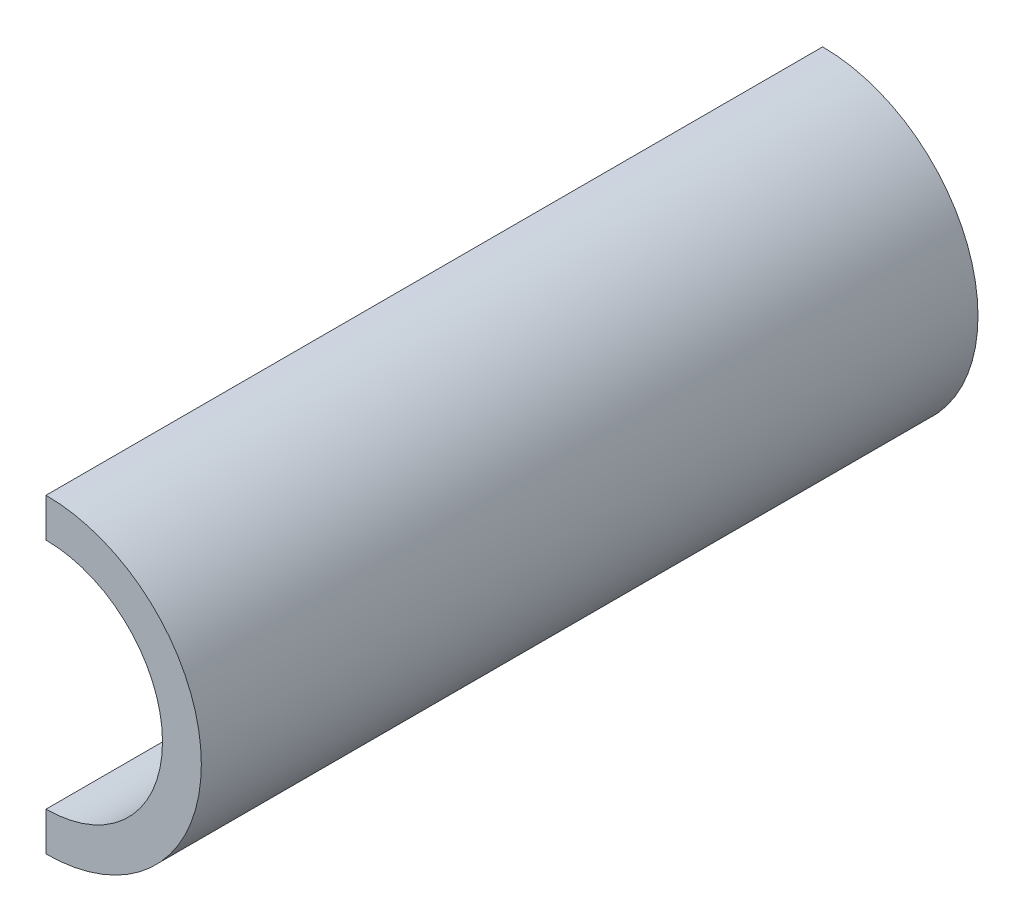
SolidWorks part; units mm, degrees
material "1.0037 (S235JR)"
ref_plane "E_Rechts" through (0, 0, 0) normal (0, 0, 1) x (1, 0, 0)
ref_plane "E_Oben" through (0, 0, 0) normal (0, 1, 0) x (1, 0, 0)
ref_plane "E_Vorne" through (0, 0, 0) normal (1, 0, 0) x (0, 0, -1)
sketch "Skizze1" plane through (0, 0, 0) normal (0, 0, 1) x (1, 0, 0)
  line L0 (0, 40) -> (0, 30)
  line L1 (0, -30) -> (0, -40)
  arc A0 (0, -40) -> (0, 40) centre (0, 0) ccw
  arc A1 (0, -30) -> (0, 30) centre (0, 0) ccw
extrude "Aufsatz-Linear austragen1" add sketch "Skizze1" along normal mid plane 200
